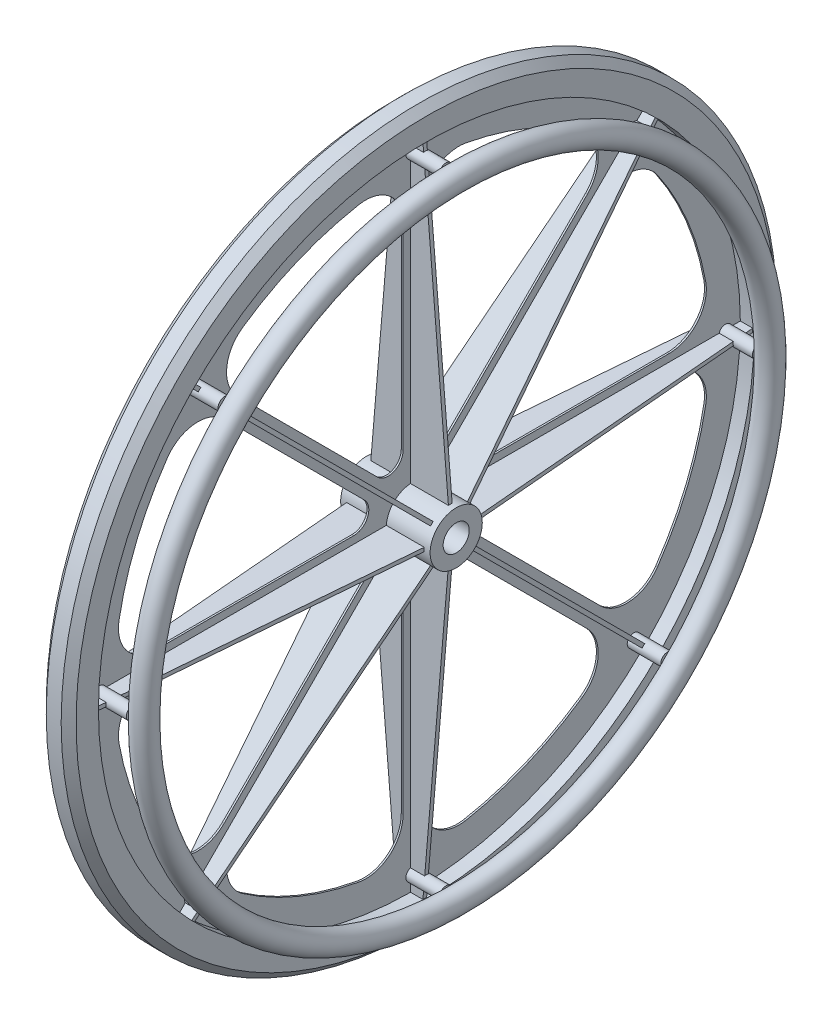
SolidWorks part; units mm, degrees
ref_plane "Alzado" through (0, 0, 0) normal (0, 0, 1) x (1, 0, 0)
ref_plane "Planta" through (0, 0, 0) normal (0, 1, 0) x (1, 0, 0)
ref_plane "Vista lateral" through (0, 0, 0) normal (1, 0, 0) x (0, 0, -1)
sketch "Croquis1" plane through (0, 0, 0) normal (1, 0, 0) x (0, 0, -1)
  circle A0 centre (0, 0) radius 22.225
  dimension "D1" = 44.45
extrude "Saliente-Extruir1" add sketch "Croquis1" along normal blind 38.1 and the other way blind 38.1
sketch "Croquis2" plane through (0, 0, 0) normal (1, 0, 0) x (0, 0, -1)
  circle A0 centre (0, 0) radius 304.8
  dimension "D1" = 609.6
extrude "Saliente-Extruir3" add sketch "Croquis2" along normal blind 0.762 and the other way blind 0.762
sketch "Croquis3" plane through (0, 0, 0) normal (1, 0, 0) x (0, 0, -1)
  circle A0 centre (0, 0) radius 304.8 construction
  circle A1 centre (0, 0) radius 304.8
  circle A2 centre (0, 0) radius 279.4
  dimension "D1" = 25.4
extrude "Saliente-Extruir4" add sketch "Croquis3" along normal blind 12.7 and the other way blind 12.7
sketch "Croquis4" plane through (0.762, 0, 0) normal (1, 0, 0) x (0, 0, -1)
  line L0 (0, 0) -> (0, 304.8) construction
  line L1 (0, 0) -> (215.5261, 215.5261) construction
  line L2 (7.9375, 218.6778) -> (7.9375, 49.8233)
  line L3 (29.6178, 40.8431) -> (149.0159, 160.2412)
  circle A0 centre (0, 0) radius 304.8 construction
  circle A1 centre (0, 0) radius 304.8 construction
  circle A2 centre (0, 0) radius 279.4 construction
  circle A3 centre (0, 0) radius 279.4
  arc A4 (144.646, 208.7907) -> (45.3571, 249.9174) centre (0, 0) ccw
  arc A5 (7.9375, 49.8233) -> (29.6178, 40.8431) centre (20.6375, 49.8233) ccw
  arc A6 (149.0159, 160.2412) -> (144.646, 208.7907) centre (126.5652, 182.6918) ccw
  arc A7 (7.9375, 218.6778) -> (45.3571, 249.9174) centre (39.6875, 218.6778) cw
  circle A8 centre (0, 0) radius 254 construction
  dimension "D5" = 12.7
  dimension "D6" = 31.75
  dimension "D7" = 31.75
  dimension "D1" = 45
  dimension "D3" = 15.875
  dimension "D4" = 15.875
  dimension "D2" = 50.8
extrude "Cortar-Extruir2" cut sketch "Croquis4" against normal through all contours A4 A7 L2 A5 L3 A6
ref_plane "Plano3" through (0, 281.94, 0) normal (0, 1, 0) x (1, 0, 0)
sketch "Croquis9" plane through (0, 0, 0) normal (0, 1, 0) x (1, 0, 0)
  line L0 (38.1, -22.225) -> (38.1, 22.225) construction
  line L1 (-34.925, 1.5875) -> (34.925, 1.5875)
  line L2 (-34.925, 1.5875) -> (-34.925, -1.5875)
  line L3 (-34.925, -1.5875) -> (34.925, -1.5875)
  line L4 (34.925, 1.5875) -> (34.925, -1.5875)
  line L5 (-34.925, 1.5875) -> (34.925, -1.5875) construction
  line L6 (-34.925, -1.5875) -> (34.925, 1.5875) construction
  point P0 (0, 0)
  dimension "D1" = 3.175
  dimension "D2" = 3.175
sketch "Croquis10" plane through (0, 281.94, 0) normal (0, 1, 0) x (1, 0, 0)
  line L1 (-11.1125, 1.5875) -> (11.1125, 1.5875)
  line L2 (-11.1125, 1.5875) -> (-11.1125, -1.5875)
  line L3 (-11.1125, -1.5875) -> (11.1125, -1.5875)
  line L4 (11.1125, 1.5875) -> (11.1125, -1.5875)
  line L5 (-11.1125, 1.5875) -> (11.1125, -1.5875) construction
  line L6 (-11.1125, -1.5875) -> (11.1125, 1.5875) construction
  point P0 (0, 0)
  dimension "D1" = 22.225
  dimension "D2" = 3.175
loft "Recubrir10" add profiles "Croquis9", "Croquis10" connector at (34.925, 0, -1.5875) connector at (11.1125, 281.94, -1.5875)
sketch "Croquis13" plane through (0.762, 0, 0) normal (1, 0, 0) x (0, 0, -1)
  line L0 (0, 279.4) -> (0, 0) construction
  arc A0 (1.5875, 279.3955) -> (-1.5875, 279.3955) centre (0, 0) ccw construction
  circle A1 centre (0, 266.7) radius 5.5565
  dimension "D1" = 11.113
  dimension "D2" = 266.7
extrude "Saliente-Extruir5" add sketch "Croquis13" along normal blind 28.575
pattern_circular "MatrizC1" count 8 over 360 about axis through (12.7, 0, 0) along (1, 0, 0) of "Saliente-Extruir5", "Cortar-Extruir2", "Recubrir10"
sketch "Croquis14" plane through (-38.1, 0, 0) normal (-1, 0, 0) x (0, 0, 1)
  circle A0 centre (0, 0) radius 11.1125
  dimension "D1" = 22.225
extrude "Cortar-Extruir3" cut sketch "Croquis14" against normal through all
sketch "Croquis15" plane through (0, 0, 0) normal (0, 0, 1) x (1, 0, 0)
  line L0 (38.862, 266.7) -> (-10.2023, 266.7) construction
  line L2 (29.337, 272.2565) -> (29.337, 266.7) construction
  line L3 (29.337, 261.1435) -> (29.337, 272.2565) construction
  circle A0 centre (38.862, 266.7) radius 9.525
  dimension "D1" = 19.05
ref_axis "Eje1" through (-42.4243, 0, 0) along (1, 0, 0)
revolve "Revolución1" add sketch "Croquis15" angle 360 about axis through (-42.4243, 0, 0) along (1, 0, 0)
chamfer "Chaflán1" distance 6.35 angle 45 2 edges at (-12.7, 0, -304.8) (12.7, 0, -304.8)
